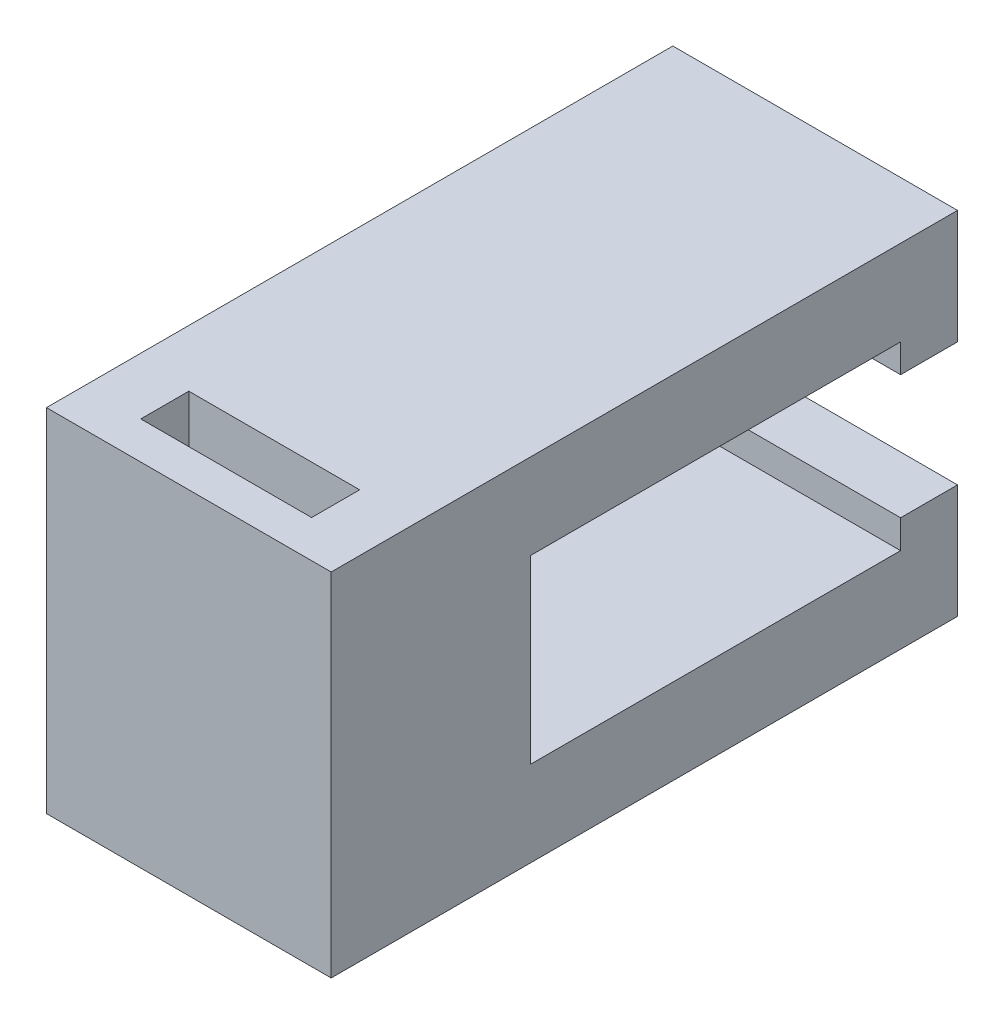
SolidWorks part; units mm, degrees
ref_plane "Front Plane" through (0, 0, 0) normal (0, 0, 1) x (1, 0, 0)
ref_plane "Top Plane" through (0, 0, 0) normal (0, 1, 0) x (1, 0, 0)
ref_plane "Right Plane" through (0, 0, 0) normal (1, 0, 0) x (0, 0, -1)
sketch "Sketch1" plane through (0, 0, 0) normal (1, 0, 0) x (0, 0, -1)
  line L5 (10.9948, 4.8363) -> (-11.0052, 4.8363)
  line L12 (5.9948, 0.2488) -> (5.9948, -2.9262) construction
  line L15 (10.9948, 4.8363) -> (10.9948, 0.8363)
  line L16 (10.9948, 0.8363) -> (8.9948, 0.8363)
  line L17 (8.9948, 0.8363) -> (8.9948, 1.8363)
  line L18 (8.9948, 1.8363) -> (-4.0052, 1.8363)
  line L19 (-4.0052, 1.8363) -> (-4.0052, -4.5137)
  line L20 (-11.0052, 4.8363) -> (-11.0052, -7.5137)
  line L21 (8.9948, -4.5137) -> (-4.0052, -4.5137)
  line L22 (8.9948, -3.5137) -> (8.9948, -4.5137)
  line L23 (10.9948, -3.5137) -> (8.9948, -3.5137)
  line L25 (10.9948, -7.5137) -> (-11.0052, -7.5137)
  line L26 (10.9948, -3.5137) -> (10.9948, -7.5137)
  line L28 (-4.0052, 0.2488) -> (-4.0052, -2.9262) construction
  point P16 (-11.0052, -1.3387)
  point P17 (-4.0052, -1.3387)
  point P24 (-4.0052, -1.3387)
  dimension "D2" = 3
  dimension "D3" = 1
  dimension "D1" = 7
  dimension "D4" = 2
  dimension "D5" = 3
extrude "MainBody" add sketch "Sketch1" along normal mid plane 10
sketch "Sketch5" plane through (0, 4.8363, 0) normal (0, 1, 0) x (1, 0, 0)
  line L1 (3, -9.6927) -> (-3, -9.6927)
  line L2 (3, -9.6927) -> (3, -8.0052)
  line L3 (3, -8.0052) -> (-3, -8.0052)
  line L4 (-3, -9.6927) -> (-3, -8.0052)
  line L5 (3, -9.6927) -> (-3, -8.0052) construction
  line L6 (3, -8.0052) -> (-3, -9.6927) construction
  line L9 (-3, -7.0052) -> (3, -7.0052) construction
  line L11 (-2.5, -8.0052) -> (2.5, -8.0052) construction
  point P0 (0, -8.8489)
  point P10 (0, -8.0052)
  dimension "D3" = 1.6875
  dimension "D1" = 6
  dimension "D2" = 2
extrude "HeightBarSlot" cut sketch "Sketch5" against normal offset from surface (7.35 mm away) 5 up to face at (0, -7.5137, 0.0052)
equation "\"HeightBarThickness\"=1.5875"
equation "\"D3@Sketch5\" = \"HeightBarThickness\" + \"HeightBarTolerance\""
equation "\"HeightBarWidth\"=6"
equation "\"D1@Sketch5\"=\"HeightBarWidth\""
equation "\"SheetThickness\"=-1.5875"
equation "\"D2@Sketch1\"=3mm"
equation "\"HeightBarTolerance\"= 0.1mm"
